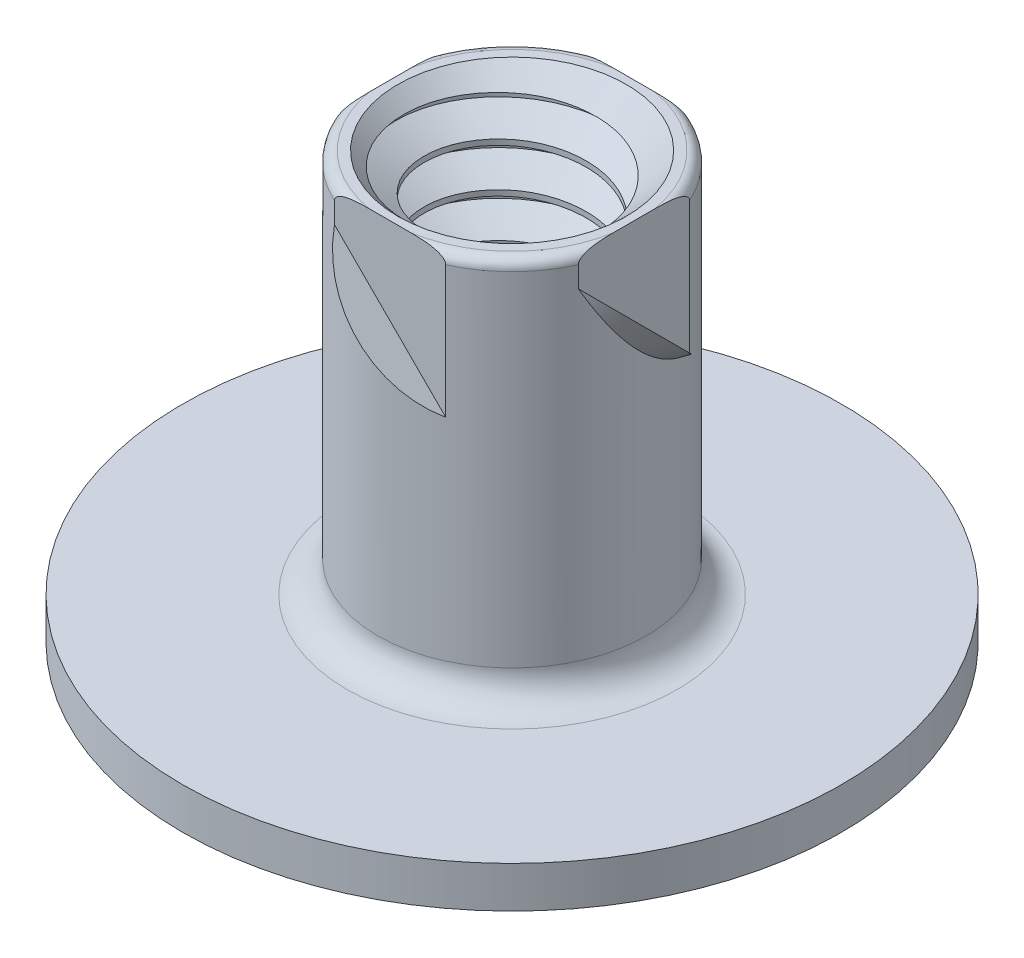
SolidWorks part; units mm, degrees
ref_plane "Front Plane" through (0, 0, 0) normal (0, 0, 1) x (1, 0, 0)
ref_plane "Top Plane" through (0, 0, 0) normal (0, 1, 0) x (1, 0, 0)
ref_plane "Right Plane" through (0, 0, 0) normal (1, 0, 0) x (0, 0, -1)
sketch "Sketch1" plane through (0, 0, 0) normal (0, 1, 0) x (1, 0, 0)
  line L0 (-9.525, 0) -> (9.525, 0) construction
  line L9 (0, 9.525) -> (0, -9.525) construction
  circle A0 centre (0, 0) radius 3.8735 construction
  circle A2 centre (0, 0) radius 3.175
  circle A3 centre (0, 0) radius 9.525 construction
  circle A4 centre (0, 0) radius 4.4704 construction
  point P2 (0, 4.4704)
  point P3 (0, 3.8735)
  point P11 (0, 3.175)
  point P15 (0, -3.175)
  point P17 (0, -3.8735)
  point P18 (0, -4.4704)
  dimension "D1" = 0.6985
sketch "Sketch2" plane through (0, 0, 0) normal (0, 0, 1) x (1, 0, 0)
  line L0 (0, 0) -> (0, 1.1938) construction
  line L1 (0, 1.1938) -> (0, 12.3063) construction
  line L4 (0, 0) -> (-9.525, 0) construction
  point P6 (0, 7.8613)
sketch "Sketch3" plane through (0, 0, 0) normal (0, 1, 0) x (1, 0, 0)
  circle A0 centre (0, 0) radius 9.525 construction
  circle A2 centre (0, 0) radius 9.525
extrude "Extrude1" add sketch "Sketch3" along normal up to vertex (1.1938 mm away) up to point (0, 1.1938, 0)
sketch "Sketch4" plane through (0, 1.1938, 0) normal (0, 1, 0) x (1, 0, 0)
  circle A1 centre (0, 0) radius 3.8735
  circle A2 centre (0, 0) radius 3.8735 construction
extrude "Extrude2" add sketch "Sketch4" along normal up to vertex (11.1125 mm away) up to point (0, 12.3063, 0)
sketch "Sketch5" plane through (0, 0, 0) normal (0, -1, 0) x (1, 0, 0)
  circle A0 centre (0, 0) radius 3.175 construction
  circle A1 centre (0, 0) radius 3.175
extrude "Extrude3" cut sketch "Sketch5" against normal up to vertex (1.1938 mm away) up to point (0, 1.1938, 0)
sketch "Sketch6" plane through (0, 1.1938, 0) normal (0, -1, 0) x (1, 0, 0)
  circle A0 centre (0, 0) radius 3.175 construction
  circle A1 centre (0, 0) radius 3.175
extrude "Extrude4" cut sketch "Sketch6" against normal up to vertex (11.1125 mm away) draft 45 up to point (0, 12.3063, 0)
fillet "Fillet1" radius 1.1938 1 edges at (0, 0, -3.175)
fillet "Fillet2" radius 0.8954 1 edges at (0, 1.1938, 3.8735)
fillet "Fillet3" radius 0.2984 1 edges at (0, 12.3063, 3.8735)
sketch "Sketch7" plane through (0, 12.3063, 0) normal (0, 1, 0) x (1, 0, 0)
  circle A0 centre (0, 0) radius 3.175 construction
  circle A1 centre (0, 0) radius 3.175
  point P3 (-3.175, 0)
curve "Helix/Spiral1" pitch 1.27 height 13.5763 radius 3.175 centre (0, 12.3063, 0) axis (0, -1, 0) start towards (0, 0, 1) parameters "Height"=13.5763, "Pitch"=1.27
sketch "Sketch8" plane through (0, 0, 0) normal (0, 0, 1) x (1, 0, 0)
  line L0 (-2.2126, 13.5366) -> (-3.3125, 12.9016) construction
  line L1 (-3.3125, 12.9016) -> (-2.2126, 12.2666) construction
  line L2 (-2.2126, 12.2666) -> (-2.2126, 13.5366) construction
  line L3 (-3.175, 12.981) -> (-3.175, 12.8222)
  line L4 (-2.3501, 13.4572) -> (-2.3501, 12.346) construction
  line L5 (-3.3125, 12.9016) -> (-3.175, 12.9016) construction
  line L6 (-2.3501, 12.9016) -> (-2.2126, 12.9016) construction
  line L7 (-3.175, 12.981) -> (-2.2814, 13.4969)
  line L8 (-2.2814, 13.4969) -> (-2.2814, 12.3063)
  line L9 (-2.2814, 12.3063) -> (-3.175, 12.8222)
  point P11 (-2.2814, 12.9016)
  dimension "D1" = 1.27
  dimension "D2" = 0.1588
sketch "Sketch9" plane through (0, 12.3063, 0) normal (0, 1, 0) x (1, 0, 0)
  circle A0 centre (0, 0) radius 2.3501
extrude "Extrude5" cut sketch "Sketch9" against normal through all
chamfer "Chamfer1" distance 0.9525 angle 45 1 edges at (0, 12.3063, 2.3501)
sweep "Cut-Sweep1" cut profiles "Sketch8" path "Helix/Spiral1" align with end faces yes
ref_plane "Plane1" through (0, 0, 3.8735) normal (0, 0, 1) x (1, 0, 0)
sketch "Sketch10" plane through (0, 0, 3.8735) normal (0, 0, 1) x (1, 0, 0)
  line L0 (1.9367, 7.8613) -> (-1.9367, 11.7348)
  line L1 (1.9367, 7.8613) -> (-1.9367, 7.8613) construction
  line L2 (-1.9367, 7.8613) -> (-1.9367, 11.7348) construction
  line L3 (-1.9367, 11.7348) -> (-1.9367, 12.3063)
  line L4 (3.3026, 12.3063) -> (-3.3026, 12.3063) construction
  line L5 (-1.9367, 12.3063) -> (1.9367, 12.3063)
  line L6 (1.9367, 12.3063) -> (1.9367, 7.8613)
  dimension "D1" = 3.8735
extrude "Extrude6" cut sketch "Sketch10" against normal blind 0.3492
sketch "Sketch11" plane through (4.899, 4.899, 0) normal (0.7071, 0.7071, 0) x (0, 0, -1)
  line L0 (-3.5242, 6.9283) -> (0, 6.9283) construction
  line L1 (0, 0.8441) -> (0, 8.7019) construction
  line L2 (-4.4704, 6.9283) -> (4.4704, 6.9283) construction
  line L3 (-3.5242, 9.2014) -> (-3.5242, 4.6551) construction
  line L4 (-3.5242, 9.2014) -> (-3.5242, 4.6551)
  arc A0 (-3.5242, 9.2014) -> (-3.5242, 4.6551) centre (-1.2666, 6.9283) ccw
  circle A1 centre (0, 6.9283) radius 4.4704 construction
  dimension "D2" = 8.9408
  dimension "D3" = 0.9461
extrude "Extrude7" add sketch "Sketch11" against normal blind 0.9461 draft 45
ref_axis "Axis1" through (0, 1.1938, 0) along (0, 1, 0)
pattern_circular "CirPattern2" count 4 over 360 about axis through (0, 1.1938, 0) along (0, 1, 0) of "Extrude6", "Extrude7"
equation "\"D1@Fillet1\" = \"T@Sketch2\""
equation "\"D1@Fillet2\" = \"T@Sketch2\" * 3 / 4"
equation "\"D1@Fillet3\" = \"T@Sketch2\"  * 1 / 4"
equation "\"Height@Helix/Spiral1\" = \"Pitch@Helix/Spiral1\" + \"B@Sketch2\" + \"T@Sketch2\""
equation "\"D1@Sketch8\" = \"Pitch@Helix/Spiral1\""
equation "\"D2@Sketch8\" = \"D1@Sketch8\" * 1 / 8"
equation "\"D1@Chamfer1\" =  \"D1@Sketch8\" * 6 / 8"
equation "\"D1@Sketch10\" = \"C@Sketch1\" * 1 / 2"
equation "\"D1@Extrude6\" = \"D1@Sketch1\" * 1 / 2"
equation "\"D2@Sketch11\" = \"S@Sketch1\""
equation "\"D1@Extrude7\" = \"D3@Sketch11\""
